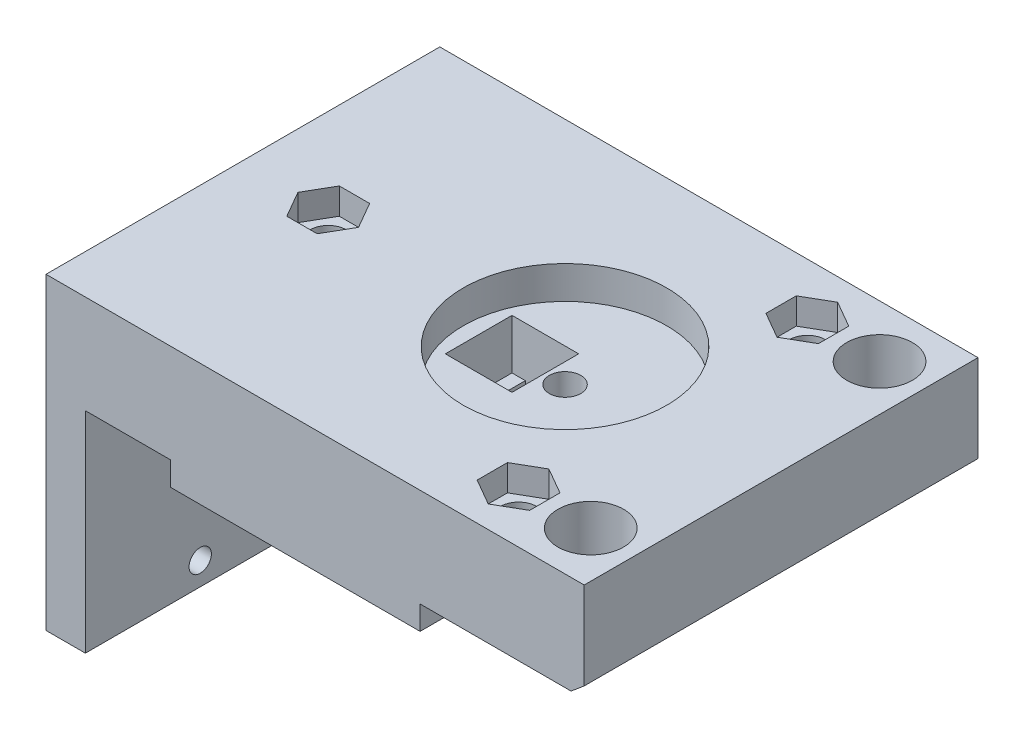
SolidWorks part; units mm, degrees
ref_plane "Front Plane" through (0, 0, 0) normal (0, 0, 1) x (1, 0, 0)
ref_plane "Top Plane" through (0, 0, 0) normal (0, 1, 0) x (1, 0, 0)
ref_plane "Right Plane" through (0, 0, 0) normal (1, 0, 0) x (0, 0, -1)
sketch "Sketch1" plane through (0, 0, 0) normal (0, 1, 0) x (1, 0, 0)
  line L1 (0, 0) -> (82, 0)
  line L2 (0, 0) -> (0, 60)
  line L3 (0, 60) -> (82, 60)
  line L4 (82, 0) -> (82, 60)
  dimension "D1" = 82
  dimension "D2" = 60
extrude "Boss-Extrude1" add sketch "Sketch1" along normal blind 15
sketch "Sketch2" plane through (0, 0, 0) normal (0, -1, 0) x (1, 0, 0)
  line L0 (0, 0) -> (82, 0) construction
  line L1 (0, -60) -> (6, -60)
  line L2 (0, -60) -> (0, 0)
  line L3 (0, 0) -> (6, 0)
  line L4 (6, -60) -> (6, 0)
  dimension "D1" = 6
extrude "Boss-Extrude2" add sketch "Sketch2" along normal blind 32
sketch "Sketch3" plane through (0, 0, 0) normal (-1, 0, 0) x (0, 0, 1)
  line L0 (0, -16) -> (-60, -16) construction
  line L1 (0, 15) -> (0, -32) construction
  line L2 (-60, 15) -> (-60, -32) construction
  line L5 (-60, -32) -> (-60, 0) construction
  line L6 (-17.5, -3.5) -> (-42.5, -3.5)
  line L7 (-17.5, -3.5) -> (-17.5, -28.5)
  line L8 (-17.5, -28.5) -> (-42.5, -28.5)
  line L9 (-42.5, -3.5) -> (-42.5, -28.5)
  line L10 (-17.5, -3.5) -> (-42.5, -28.5) construction
  line L11 (-17.5, -28.5) -> (-42.5, -3.5) construction
  point P7 (-30, -16)
  dimension "D1" = 25
hole_wizard "M3 Clearance Hole1" positions "Sketch4" profile "Sketch5" hole size "M3" standard "ANSI Metric" end condition through all
sketch "Sketch4" plane through (0, 0, 0) normal (-1, 0, 0) x (0, 0, 1)
  point P0 (-42.5, -28.5)
  point P3 (-42.5, -3.5)
  point P6 (-17.5, -3.5)
  point P9 (-17.5, -28.5)
sketch "Sketch5" plane through (0, -28.5, -42.5) normal (0, 1, 0) x (0, 0, 1)
  line L0 (0, 0) -> (0, 82)
  line L1 (0, 82) -> (1.7, 82)
  line L2 (1.7, 82) -> (1.7, 0)
  line L5 (1.7, 0) -> (0, 0)
  line L11 (0, -6.35) -> (0, 107.95) construction
  dimension "Thru Hole Dia." = 3.4
  dimension "Thru Hole Depth" = 82
ref_plane "Plane1" through (0, -16, 0) normal (0, -1, 0) x (-1, 0, 0)
ref_plane "Plane2" through (0, -4, 0) normal (0, -1, 0) x (-1, 0, 0)
ref_plane "Belt Plane" through (0, -3.624, 0) normal (0, -1, 0) x (-1, 0, 0)
sketch "Sketch7" plane through (0, 0, 0) normal (0, -1, 0) x (1, 0, 0)
  line L0 (82, -60) -> (6, -60) construction
  line L1 (19, -60) -> (57, -60)
  line L2 (19, -60) -> (19, 0)
  line L3 (19, 0) -> (57, 0)
  line L4 (57, -60) -> (57, 0)
  line L5 (6, 0) -> (82, 0) construction
  line L6 (6, -60) -> (6, 0) construction
  line L8 (82, 0) -> (82, -60) construction
  dimension "D1" = 13
  dimension "D2" = 25
extrude "Boss-Extrude3" add sketch "Sketch7" along normal up to surface (3.624 mm away) up to plane "Belt Plane"
sketch "Sketch8" plane through (0, -3.624, 0) normal (0, -1, 0) x (1, 0, 0)
  line L0 (41, -60) -> (41, 0) construction
  line L1 (19, -60) -> (57, -60) construction
  line L2 (57, 0) -> (19, 0) construction
  line L4 (6, -60) -> (6, 0) construction
  dimension "D1" = 35
hole_wizard "M4 Clearance Hole1" positions "Sketch9" profile "Sketch10" hole size "M4" standard "ANSI Metric" end condition through all
sketch "Sketch9" plane through (0, -3.624, 0) normal (0, -1, 0) x (-1, 0, 0)
  line L0 (-41, 60) -> (-41, 0) construction
  point P0 (-41, 30)
sketch "Sketch10" plane through (41, -3.624, -30) normal (1, 0, 0) x (0, 0, -1)
  line L0 (0, 0) -> (0, 18.624)
  line L1 (0, 18.624) -> (2.25, 18.624)
  line L2 (2.25, 18.624) -> (2.25, 0)
  line L5 (2.25, 0) -> (0, 0)
  line L11 (0, -6.35) -> (0, 107.95) construction
  dimension "Thru Hole Dia." = 4.5
  dimension "Thru Hole Depth" = 18.624
sketch "Sketch11" plane through (0, 15, 0) normal (0, 1, 0) x (1, 0, 0)
  line L1 (35.92, 24.92) -> (46.08, 24.92)
  line L2 (35.92, 24.92) -> (35.92, 35.08)
  line L3 (35.92, 35.08) -> (46.08, 35.08)
  line L4 (46.08, 24.92) -> (46.08, 35.08)
  line L5 (35.92, 24.92) -> (46.08, 35.08) construction
  line L6 (35.92, 35.08) -> (46.08, 24.92) construction
  point P0 (41, 30)
  dimension "D1" = 10.16
extrude "Cut-Extrude1" cut sketch "Sketch11" against normal offset from surface (14.124 mm away) 4.5 up to face at (41, -3.624, -32.25)
sketch "Sketch12" plane through (0, 0.876, 0) normal (0, 1, 0) x (1, 0, 0)
  line L0 (46.08, 35.08) -> (35.92, 35.08) construction
  line L1 (35.92, 24.92) -> (37.952, 24.92)
  line L2 (35.92, 24.92) -> (35.92, 35.08)
  line L3 (35.92, 35.08) -> (37.952, 35.08)
  line L4 (37.952, 24.92) -> (37.952, 35.08)
  line L6 (46.08, 24.92) -> (44.048, 24.92)
  line L7 (46.08, 24.92) -> (46.08, 35.08)
  line L8 (46.08, 35.08) -> (44.048, 35.08)
  line L9 (44.048, 24.92) -> (44.048, 35.08)
  dimension "D1" = 6.096
extrude "Boss-Extrude4" add sketch "Sketch12" along normal blind 1.524
ref_plane "Plane4" through (41, 0, 0) normal (-1, 0, 0) x (0, 0, 1)
sketch "Sketch15" plane through (0, 15, 0) normal (0, 1, 0) x (1, 0, 0)
  line L0 (75, 60) -> (75, 0) construction
  line L1 (82, 60) -> (0, 60) construction
  line L2 (0, 0) -> (82, 0) construction
  line L3 (82, 0) -> (82, 60) construction
  point P8 (75, 52)
  point P9 (75, 8)
  dimension "D1" = 7
  dimension "D2" = 8
  dimension "D3" = 8
hole_wizard "CBORE for M5 SHCS2" positions "Sketch18" profile "Sketch19" counterbore size "M5" standard "ANSI Metric" end condition through all
sketch "Sketch18" plane through (0, 15, 0) normal (0, 1, 0) x (1, 0, 0)
  point P0 (75, 52)
  point P3 (75, 8)
sketch "Sketch19" plane through (75, 15, -52) normal (1, 0, 0) x (0, 0, 1)
  line L0 (0, 0) -> (0, 47)
  line L1 (0, 47) -> (2.75, 47)
  line L3 (2.75, 47) -> (2.75, 10)
  line L4 (2.75, 10) -> (5, 10)
  line L5 (5, 10) -> (5, 0)
  line L7 (5, 0) -> (0, 0)
  line L11 (0, -6.35) -> (0, 107.95) construction
  dimension "Thru Hole Dia." = 5.5
  dimension "Thru Hole Depth" = 47
  dimension "C'Bore Dia." = 10
  dimension "C'Bore Depth" = 10
chamfer "Chamfer1" distance 2 angle 40 1 edges at (82, 0, -30) first distance on face at (75, 0, -54.75)
sketch "Sketch20" plane through (0, 15, 0) normal (0, 1, 0) x (1, 0, 0)
  line L0 (64, 0) -> (64, 60) construction
  line L1 (0, 0) -> (82, 0) construction
  line L2 (82, 60) -> (0, 60) construction
  line L3 (64, 60) -> (13, 30) construction
  line L5 (13, 30) -> (64, 0) construction
  line L6 (13, 30) -> (0, 30) construction
  line L7 (0, 60) -> (0, 0) construction
  line L8 (64, 12.6188) -> (60, 10.3094)
  line L9 (60, 10.3094) -> (60, 5.6906)
  line L10 (60, 5.6906) -> (64, 3.3812)
  line L11 (64, 3.3812) -> (68, 5.6906)
  line L12 (68, 5.6906) -> (68, 10.3094)
  line L13 (68, 10.3094) -> (64, 12.6188)
  line L14 (64, 47.3812) -> (68, 49.6906)
  line L15 (68, 49.6906) -> (68, 54.3094)
  line L16 (68, 54.3094) -> (64, 56.6188)
  line L17 (64, 56.6188) -> (60, 54.3094)
  line L18 (60, 54.3094) -> (60, 49.6906)
  line L19 (60, 49.6906) -> (64, 47.3812)
  line L20 (10.6906, 26) -> (15.3094, 26)
  line L21 (15.3094, 26) -> (17.6188, 30)
  line L22 (17.6188, 30) -> (15.3094, 34)
  line L23 (15.3094, 34) -> (10.6906, 34)
  line L24 (10.6906, 34) -> (8.3812, 30)
  line L25 (8.3812, 30) -> (10.6906, 26)
  line L26 (82, 0) -> (82, 60) construction
  circle A0 centre (64, 8) radius 4 construction
  circle A1 centre (64, 52) radius 4 construction
  circle A2 centre (13, 30) radius 4 construction
  dimension "D1" = 13
  dimension "D2" = 8
  dimension "D3" = 8
  dimension "D4" = 8
  dimension "D5" = 18
extrude "Cut-Extrude2" cut sketch "Sketch20" against normal blind 4
sketch "Sketch21" plane through (0, 0, 0) normal (0, -1, 0) x (1, 0, 0)
  line L0 (68, -10.3094) -> (64, -12.6188) construction
  line L1 (64, -12.6188) -> (60, -10.3094) construction
  line L2 (60, -10.3094) -> (60, -5.6906) construction
  line L3 (60, -5.6906) -> (64, -3.3812) construction
  line L4 (64, -3.3812) -> (68, -5.6906) construction
  line L5 (68, -5.6906) -> (68, -10.3094) construction
  line L6 (60, -49.6906) -> (64, -47.3812) construction
  line L7 (64, -47.3812) -> (68, -49.6906) construction
  line L8 (68, -49.6906) -> (68, -54.3094) construction
  line L9 (68, -54.3094) -> (64, -56.6188) construction
  line L10 (64, -56.6188) -> (60, -54.3094) construction
  line L11 (60, -54.3094) -> (60, -49.6906) construction
  line L12 (68, -10.3094) -> (64, -12.6188)
  line L13 (64, -12.6188) -> (60, -10.3094)
  line L14 (60, -10.3094) -> (60, -5.6906)
  line L15 (60, -5.6906) -> (64, -3.3812)
  line L16 (64, -3.3812) -> (68, -5.6906)
  line L17 (68, -5.6906) -> (68, -10.3094)
  line L18 (60, -49.6906) -> (64, -47.3812)
  line L19 (64, -47.3812) -> (68, -49.6906)
  line L20 (68, -49.6906) -> (68, -54.3094)
  line L21 (68, -54.3094) -> (64, -56.6188)
  line L22 (64, -56.6188) -> (60, -54.3094)
  line L23 (60, -54.3094) -> (60, -49.6906)
  line L24 (64, -56.6188) -> (64, -47.3812)
  line L25 (64, -12.6188) -> (64, -3.3812)
  line L26 (10.6906, -34) -> (15.3094, -26)
  line L32 (10.6906, -26) -> (8.3812, -30)
  line L33 (15.3094, -26) -> (10.6906, -26)
  line L34 (17.6188, -30) -> (15.3094, -26)
  line L35 (15.3094, -34) -> (17.6188, -30)
  line L36 (10.6906, -34) -> (15.3094, -34)
  line L37 (8.3812, -30) -> (10.6906, -34)
  line L38 (10.6906, -26) -> (8.3812, -30)
  line L39 (15.3094, -26) -> (10.6906, -26)
  line L40 (17.6188, -30) -> (15.3094, -26)
  line L41 (15.3094, -34) -> (17.6188, -30)
  line L42 (10.6906, -34) -> (15.3094, -34)
  line L43 (8.3812, -30) -> (10.6906, -34)
  dimension "D1" = 0
hole_wizard "CBORE for M5 SHCS3" positions "Sketch22" profile "Sketch23" counterbore size "M5" standard "ANSI Metric" end condition through all
sketch "Sketch22" plane through (0, 0, 0) normal (0, -1, 0) x (-1, 0, 0)
  line L0 (-64, 12.6188) -> (-64, 3.3812) construction
  line L1 (-64, 56.6188) -> (-64, 47.3812) construction
  line L2 (-10.6906, 34) -> (-15.3094, 26) construction
  point P0 (-64, 52)
  point P2 (-64, 8)
  point P11 (-13, 30)
sketch "Sketch23" plane through (64, 0, -52) normal (1, 0, 0) x (0, 0, -1)
  line L0 (0, 0) -> (0, 15)
  line L1 (0, 15) -> (2.75, 15)
  line L3 (2.75, 15) -> (2.75, 5)
  line L4 (2.75, 5) -> (5, 5)
  line L5 (5, 5) -> (5, 0)
  line L7 (5, 0) -> (0, 0)
  line L11 (0, -6.35) -> (0, 107.95) construction
  dimension "Thru Hole Dia." = 5.5
  dimension "Thru Hole Depth" = 15
  dimension "C'Bore Dia." = 10
  dimension "C'Bore Depth" = 5
sketch "Sketch24" plane through (0, 15, 0) normal (0, 1, 0) x (1, 0, 0)
  line L0 (46.08, 30) -> (49.08, 30) construction
  line L1 (46.08, 24.92) -> (46.08, 35.08) construction
  circle A0 centre (49.08, 30) radius 16
  circle A1 centre (49.08, 30) radius 2.5
  circle A2 centre (49.08, 30) radius 2.4
  dimension "D1" = 32
  dimension "D2" = 5
  dimension "D3" = 4.8
  dimension "D4" = 3
extrude "Cut-Extrude3" cut sketch "Sketch24" against normal through all and the other way through all contours A2 region at (49.08, 15, -30)
sketch "Sketch25" plane through (0, 15, 0) normal (0, 1, 0) x (1, 0, 0)
  circle A0 centre (49.08, 30) radius 15.5
  dimension "D1" = 31
extrude "Cut-Extrude4" cut sketch "Sketch25" against normal blind 5
